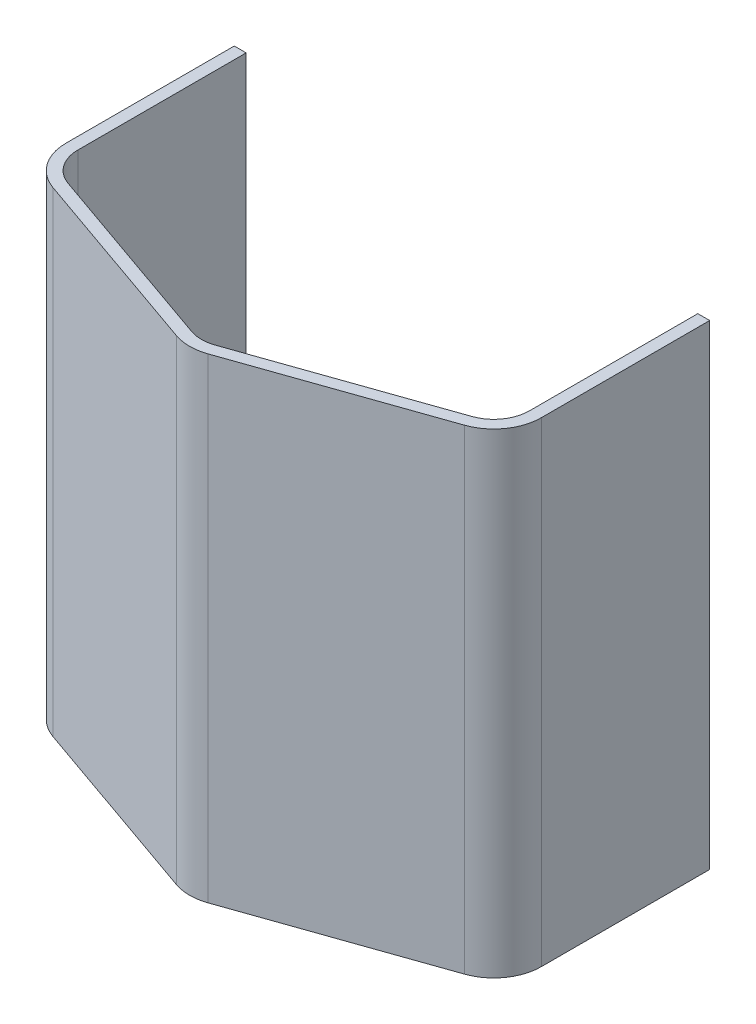
SolidWorks part; units mm, degrees
ref_plane "Front Plane" through (0, 0, 0) normal (0, 0, 1) x (1, 0, 0)
ref_plane "Top Plane" through (0, 0, 0) normal (0, 1, 0) x (1, 0, 0)
ref_plane "Right Plane" through (0, 0, 0) normal (1, 0, 0) x (0, 0, -1)
sketch "Sketch1" plane through (0, 0, 0) normal (0, 1, 0) x (1, 0, 0)
  line L0 (0, 0) -> (200, 0)
  line L1 (200, 0) -> (200, -70.8104)
  line L2 (0, 0) -> (0, -70.8104)
  line L4 (13.393, -89.6875) -> (93.393, -117.6875)
  line L5 (186.607, -89.6875) -> (106.607, -117.6875)
  arc A0 (93.393, -117.6875) -> (106.607, -117.6875) centre (100, -98.8104) ccw
  arc A1 (200, -70.8104) -> (186.607, -89.6875) centre (180, -70.8104) cw
  arc A2 (13.393, -89.6875) -> (0, -70.8104) centre (20, -70.8104) cw
  point P12 (200, -85)
  point P15 (0, -85)
  dimension "D5" = 20
  dimension "D1" = 200
  dimension "D2" = 85
  dimension "D3" = 85
extrude "Boss-Extrude1" add sketch "Sketch1" along normal blind 200 contours L2 A2 L4 A0 L5 A1 L1 L0
shell "Shell3" thickness 5 removed face at (100, 0, 70.2203) removed face at (100, 100, 0) removed face at (100, 200, 70.2203)
